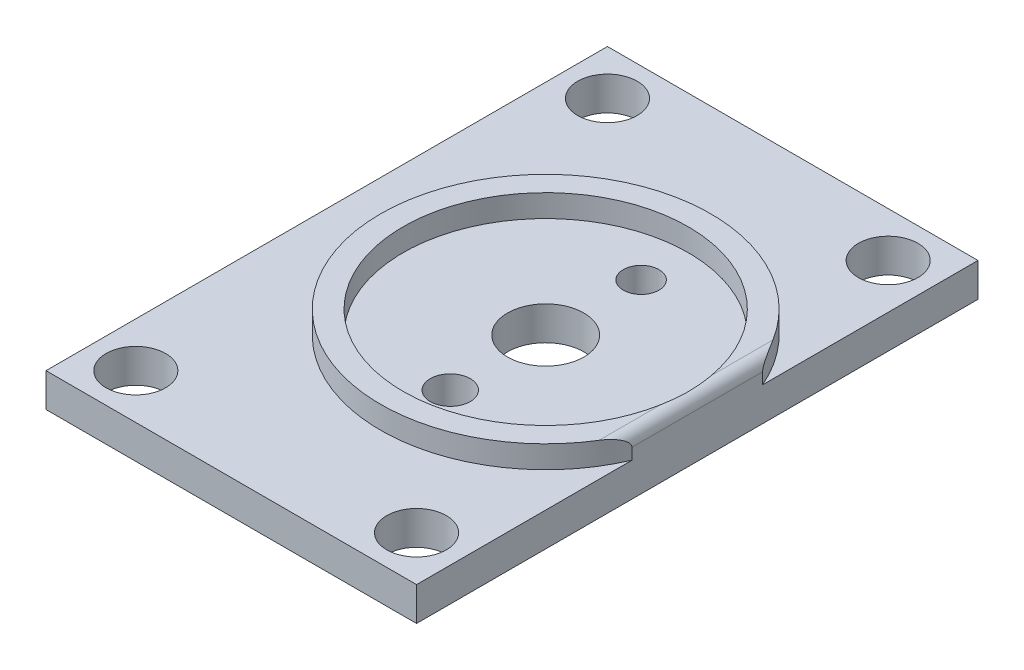
SolidWorks part; units mm, degrees
ref_plane "Front Plane" through (0, 0, 0) normal (0, 0, 1) x (1, 0, 0)
ref_plane "Top Plane" through (0, 0, 0) normal (0, 1, 0) x (1, 0, 0)
ref_plane "Right Plane" through (0, 0, 0) normal (1, 0, 0) x (0, 0, -1)
sketch "Sketch1" plane through (0, 0, 0) normal (0, 1, 0) x (1, 0, 0)
  line L1 (-10.223, 36.3848) -> (14.777, 36.3848)
  line L2 (-10.223, 36.3848) -> (-10.223, -13.6152)
  line L3 (-10.223, -13.6152) -> (14.777, -13.6152)
  line L4 (14.777, 36.3848) -> (14.777, -13.6152)
  circle A0 centre (1.277, 11.3848) radius 3.4
  dimension "D3" = 6.8
  dimension "D1" = 50
  dimension "D2" = 25
  dimension "D4" = 13.5
  dimension "D5" = 25
extrude "Boss-Extrude1" add sketch "Sketch1" along normal blind 3
sketch "Sketch2" plane through (-10.223, 0, 0) normal (-1, 0, 0) x (0, 0, 1)
  line L0 (18.15, 0) -> (-18.15, 0) construction
  line L1 (-36.3848, 3) -> (13.6152, 3)
  line L2 (-36.3848, 3) -> (-36.3848, 0)
  line L3 (-36.3848, 0) -> (13.6152, 0)
  line L4 (13.6152, 3) -> (13.6152, 0)
  line L5 (13.6152, 3) -> (13.6152, 0) construction
extrude "Boss-Extrude2" add sketch "Sketch2" along normal blind 8
sketch "Sketch3" plane through (0, 0, 0) normal (0, -1, 0) x (1, 0, 0)
  line L0 (-18.223, 13.6152) -> (14.777, 13.6152) construction
  line L1 (-18.223, -36.3848) -> (-10.223, -36.3848)
  line L2 (-18.223, -36.3848) -> (-18.223, 13.6152)
  line L3 (-18.223, 13.6152) -> (-10.223, 13.6152)
  line L4 (-10.223, -36.3848) -> (-10.223, 13.6152)
  dimension "D1" = 8
extrude "Boss-Extrude3" add sketch "Sketch3" along normal blind 42
sketch "Sketch4" plane through (0, 3, 0) normal (0, 1, 0) x (1, 0, 0)
  line L0 (-18.223, -13.6152) -> (-18.223, 36.3848) construction
  line L1 (14.777, 36.3848) -> (-18.223, 36.3848) construction
  line L2 (-18.223, -13.6152) -> (14.777, -13.6152) construction
  circle A0 centre (-14.223, 32.3848) radius 2.65
  circle A1 centre (-14.223, -9.6152) radius 2.65
  dimension "D2" = 5.3
  dimension "D4" = 5.3
  dimension "D5" = 4
  dimension "D6" = 4
  dimension "D1" = 4
  dimension "D3" = 4
extrude "Cut-Extrude1" cut sketch "Sketch4" against normal blind 3.3
ref_plane "Plane1" through (0, -19.5, 0) normal (0, 1, 0) x (1, 0, 0)
mirror "Mirror1" about plane through (0, -19.5, 0) normal (0, 1, 0) of "Cut-Extrude1"
sketch "Sketch5" plane through (-18.223, 0, 0) normal (-1, 0, 0) x (0, 0, 1)
  line L0 (18.15, 0) -> (-18.15, 0) construction
  line L1 (-6.9841, -24.1818) -> (-6.6547, -18.3888) construction
  line L2 (-6.6547, -18.3888) -> (-11.5069, -15.207) construction
  line L3 (-11.5069, -15.207) -> (-16.6885, -17.8182) construction
  line L4 (-16.6885, -17.8182) -> (-17.0179, -23.6112) construction
  line L5 (-17.0179, -23.6112) -> (-12.1657, -26.793) construction
  line L6 (-12.1657, -26.793) -> (-6.9841, -24.1818) construction
  circle A0 centre (-11.8363, -21) radius 5.025 construction
  circle A1 centre (-11.8363, -21) radius 5.8024
  dimension "D1" = 21
  dimension "D2" = 10.05
extrude "Cut-Extrude2" cut sketch "Sketch5" against normal blind 9
fillet "Fillet2" radius 1 1 edges at (-10.223, -21, -6.0339)
ref_plane "Plane2" through (-1.723, 0, 0) normal (-1, 0, 0) x (0, 0, 1)
mirror "Mirror2" about plane through (-1.723, 0, 0) normal (-1, 0, 0) of "Cut-Extrude1"
sketch "Sketch6" plane through (0, 3, 0) normal (0, 1, 0) x (1, 0, 0)
  line L0 (1.277, 14.7848) -> (1.277, 7.9848) construction
  line L1 (14.777, -13.6152) -> (14.777, 36.3848) construction
  line L2 (14.777, 17.202) -> (14.777, 5.5675)
  circle A0 centre (1.277, 11.3848) radius 3.4 construction
  circle A1 centre (1.277, 11.3848) radius 3.1
  circle A2 centre (1.277, 11.3848) radius 12.7
  arc A3 (14.777, 17.202) -> (14.777, 5.5675) centre (1.277, 11.3848) ccw
  line M9 (14.777, -13.6152) -> (14.777, 36.3848)
  dimension "D1" = 25.4
  dimension "D2" = 2
extrude "Boss-Extrude4" add sketch "Sketch6" along normal blind 2 contours A3 A2 M9 region at (14.3696, 3, -11.3848)
fillet "Fillet4" radius 1 1 edges at (14.777, 5, -11.3848)
sketch "Sketch8" plane through (0, 3, 0) normal (0, 1, 0) x (1, 0, 0)
  line L0 (4.677, 11.3848) -> (-2.123, 11.3848) construction
  circle A0 centre (1.277, 11.3848) radius 3.4 construction
  circle A1 centre (1.277, 19.8848) radius 1.5898
  circle A2 centre (1.277, 2.8848) radius 1.7774
  point P9 (1.277, 11.3848)
  dimension "D1" = 8.5
  dimension "D2" = 8.5
extrude "Cut-Extrude3" cut sketch "Sketch8" against normal blind 10
sketch "Sketch9" plane through (0, 0, 13.6152) normal (0, 0, 1) x (1, 0, 0)
  line L0 (-18.223, -42) -> (-18.223, 3) construction
  line L1 (-18.223, 0) -> (-10.223, 0)
  line L2 (-18.223, 0) -> (-18.223, -42)
  line L3 (-18.223, -42) -> (-10.223, -42)
  line L4 (-10.223, 0) -> (-10.223, -42)
extrude "Cut-Extrude4" cut sketch "Sketch9" against normal through all
